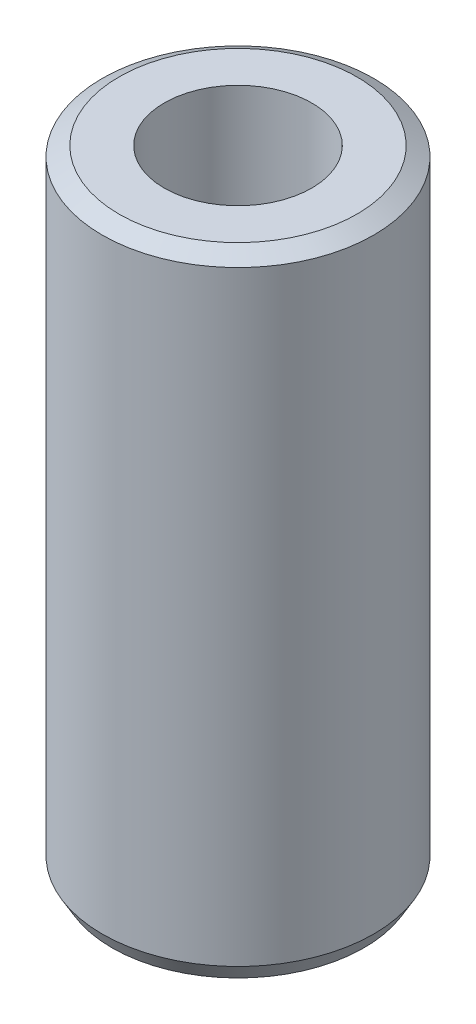
SolidWorks part; units mm, degrees
ref_plane "Front Plane" through (0, 0, 0) normal (0, 0, 1) x (1, 0, 0)
ref_plane "Top Plane" through (0, 0, 0) normal (0, 1, 0) x (1, 0, 0)
ref_plane "Right Plane" through (0, 0, 0) normal (1, 0, 0) x (0, 0, -1)
sketch "Sketch1" plane through (0, 0, 0) normal (0, 1, 0) x (1, 0, 0)
  circle A0 centre (0, 0) radius 32.5
  dimension "SHAFT_OD" = 65
extrude "Boss-Extrude1" add sketch "Sketch1" along normal blind 151.2547
sketch "Sketch2" plane through (0, 0, 0) normal (0, 1, 0) x (1, 0, 0)
  circle A0 centre (0, 0) radius 17.666
  dimension "BORE_D" = 35.3319
extrude "Cut-Extrude1" cut sketch "Sketch2" along normal through all
chamfer "Chamfer1" distance 2.3253 angle 60 2 edges at (0, 151.2547, 32.5) (0, 0, 32.5) first distance on face at (0, 151.2547, 32.5) first distance on face at (0, 0, 17.666)
